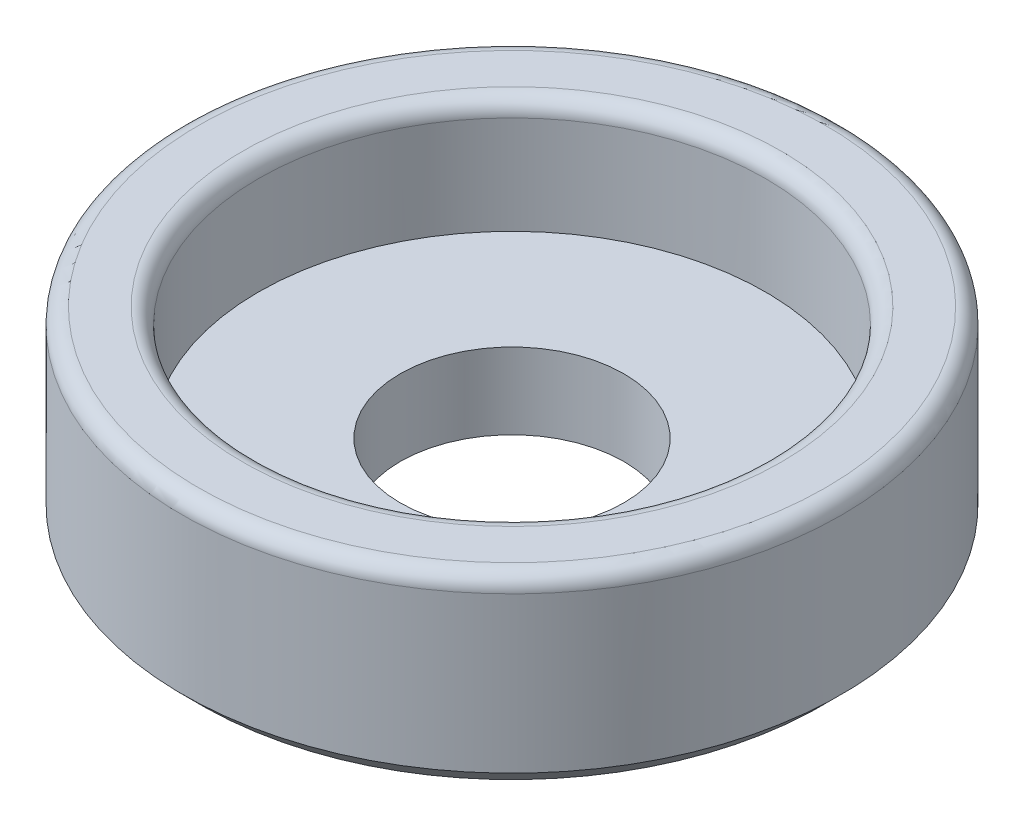
SolidWorks part; units mm, degrees
ref_plane "Front Plane" through (0, 0, 0) normal (0, 0, 1) x (1, 0, 0)
ref_plane "Top Plane" through (0, 0, 0) normal (0, 1, 0) x (1, 0, 0)
ref_plane "Right Plane" through (0, 0, 0) normal (1, 0, 0) x (0, 0, -1)
sketch "Sketch1" plane through (0, 0, 0) normal (0, 0, 1) x (1, 0, 0)
  line L0 (0, 0) -> (5.2, 0)
  line L1 (5.2, 0) -> (5.2, 3)
  line L2 (5.2, 3) -> (4, 3)
  line L3 (4, 3) -> (4, 1.2)
  line L4 (4, 1.2) -> (0, 1.2)
  line L5 (0, 1.2) -> (0, 0)
  dimension "D1" = 1.2
  dimension "D2" = 4
  dimension "D3" = 3
revolve "Revolve1" add sketch "Sketch1" angle 360 about L5
sketch "Sketch2" plane through (0, 1.2, 0) normal (0, 1, 0) x (1, 0, 0)
  circle A0 centre (0, 0) radius 1.765
  dimension "D1" = 3.53
extrude "Cut-Extrude1" cut sketch "Sketch2" against normal through all
fillet "Fillet1" radius 0.25 2 edges at (-4, 3, 0) (-5.2, 3, 0)
chamfer "Chamfer1" distance 0.3 angle 45 1 edges at (-5.2, 0, 0)
